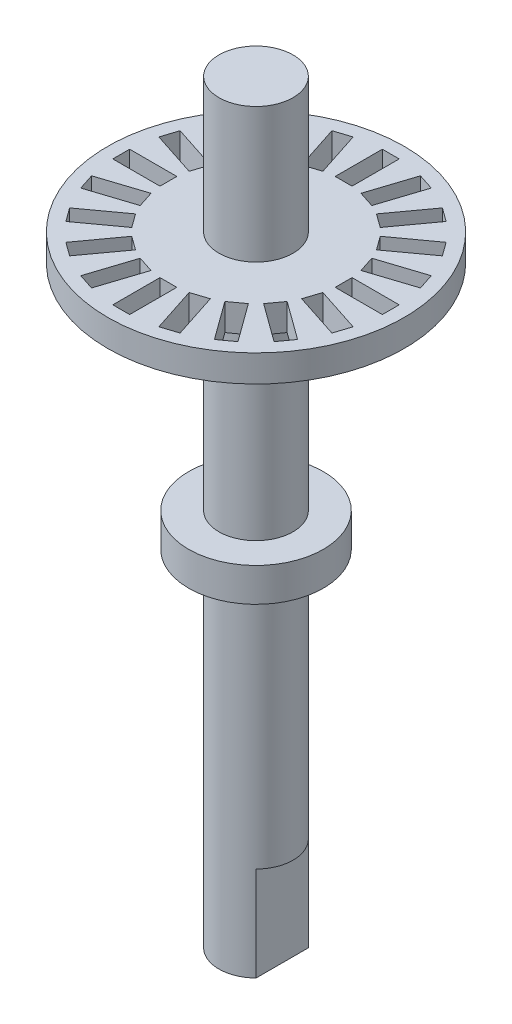
SolidWorks part; units mm, degrees
ref_plane "前视基准面" through (0, 0, 0) normal (0, 0, 1) x (1, 0, 0)
ref_plane "上视基准面" through (0, 0, 0) normal (0, 1, 0) x (1, 0, 0)
ref_plane "右视基准面" through (0, 0, 0) normal (1, 0, 0) x (0, 0, -1)
sketch "草图1" plane through (0, 0, 0) normal (0, 1, 0) x (1, 0, 0)
  circle A0 centre (0, 0) radius 2.75
  dimension "D1" = 5.5
extrude "凸台-拉伸1" add sketch "草图1" along normal blind 49
sketch "草图2" plane through (0, 0, 0) normal (0, -1, 0) x (1, 0, 0)
  line L0 (0, 0) -> (0, -4.8851) construction
  line L2 (-1.95, 1.9391) -> (-1.95, -1.9391)
  line L4 (1.95, 1.9391) -> (1.95, -1.9391)
  arc A0 (-1.95, -1.9391) -> (1.95, -1.9391) centre (0, 0) ccw
  arc A1 (1.95, 1.9391) -> (-1.95, 1.9391) centre (0, 0) ccw
  dimension "D1" = 5.5
  dimension "D2" = 3.9
extrude "凸台-拉伸2" add sketch "草图2" along normal blind 7
sketch "草图6" plane through (0, 49, 0) normal (0, 1, 0) x (1, 0, 0)
  line L2 (0, 11) -> (0, 0) construction
  line L3 (2.4958, 9.7037) -> (3.6846, 9.3174)
  line L42 (-0.625, 10) -> (0.625, 10)
  line L43 (-0.625, 10) -> (-0.625, 6.5)
  line L44 (-0.625, 6.5) -> (0.625, 6.5)
  line L45 (0.625, 10) -> (0.625, 6.5)
  line L46 (2.4958, 9.7037) -> (1.4142, 6.375)
  line L47 (1.4142, 6.375) -> (2.603, 5.9887)
  line L48 (3.6846, 9.3174) -> (2.603, 5.9887)
  line L49 (5.3722, 8.4575) -> (6.3835, 7.7228)
  line L50 (5.3722, 8.4575) -> (3.315, 5.626)
  line L51 (3.315, 5.626) -> (4.3262, 4.8912)
  line L52 (6.3835, 7.7228) -> (4.3262, 4.8912)
  line L53 (7.7228, 6.3835) -> (8.4575, 5.3722)
  line L54 (7.7228, 6.3835) -> (4.8912, 4.3262)
  line L55 (4.8912, 4.3262) -> (5.626, 3.315)
  line L56 (8.4575, 5.3722) -> (5.626, 3.315)
  line L57 (9.3174, 3.6846) -> (9.7037, 2.4958)
  line L58 (9.3174, 3.6846) -> (5.9887, 2.603)
  line L59 (5.9887, 2.603) -> (6.375, 1.4142)
  line L60 (9.7037, 2.4958) -> (6.375, 1.4142)
  line L61 (10, 0.625) -> (10, -0.625)
  line L62 (10, 0.625) -> (6.5, 0.625)
  line L63 (6.5, 0.625) -> (6.5, -0.625)
  line L64 (10, -0.625) -> (6.5, -0.625)
  line L65 (9.7037, -2.4958) -> (9.3174, -3.6846)
  line L66 (9.7037, -2.4958) -> (6.375, -1.4142)
  line L67 (6.375, -1.4142) -> (5.9887, -2.603)
  line L68 (9.3174, -3.6846) -> (5.9887, -2.603)
  line L69 (8.4575, -5.3722) -> (7.7228, -6.3835)
  line L70 (8.4575, -5.3722) -> (5.626, -3.315)
  line L71 (5.626, -3.315) -> (4.8912, -4.3262)
  line L72 (7.7228, -6.3835) -> (4.8912, -4.3262)
  line L73 (6.3835, -7.7228) -> (5.3722, -8.4575)
  line L74 (6.3835, -7.7228) -> (4.3262, -4.8912)
  line L75 (4.3262, -4.8912) -> (3.315, -5.626)
  line L76 (5.3722, -8.4575) -> (3.315, -5.626)
  line L77 (3.6846, -9.3174) -> (2.4958, -9.7037)
  line L78 (3.6846, -9.3174) -> (2.603, -5.9887)
  line L79 (2.603, -5.9887) -> (1.4142, -6.375)
  line L80 (2.4958, -9.7037) -> (1.4142, -6.375)
  line L81 (0.625, -10) -> (-0.625, -10)
  line L82 (0.625, -10) -> (0.625, -6.5)
  line L83 (0.625, -6.5) -> (-0.625, -6.5)
  line L84 (-0.625, -10) -> (-0.625, -6.5)
  line L85 (-2.4958, -9.7037) -> (-3.6846, -9.3174)
  line L86 (-2.4958, -9.7037) -> (-1.4142, -6.375)
  line L87 (-1.4142, -6.375) -> (-2.603, -5.9887)
  line L88 (-3.6846, -9.3174) -> (-2.603, -5.9887)
  line L89 (-5.3722, -8.4575) -> (-6.3835, -7.7228)
  line L90 (-5.3722, -8.4575) -> (-3.315, -5.626)
  line L91 (-3.315, -5.626) -> (-4.3262, -4.8912)
  line L92 (-6.3835, -7.7228) -> (-4.3262, -4.8912)
  line L93 (-7.7228, -6.3835) -> (-8.4575, -5.3722)
  line L94 (-7.7228, -6.3835) -> (-4.8912, -4.3262)
  line L95 (-4.8912, -4.3262) -> (-5.626, -3.315)
  line L96 (-8.4575, -5.3722) -> (-5.626, -3.315)
  line L97 (-9.3174, -3.6846) -> (-9.7037, -2.4958)
  line L98 (-9.3174, -3.6846) -> (-5.9887, -2.603)
  line L99 (-5.9887, -2.603) -> (-6.375, -1.4142)
  line L100 (-9.7037, -2.4958) -> (-6.375, -1.4142)
  line L101 (-10, -0.625) -> (-10, 0.625)
  line L102 (-10, -0.625) -> (-6.5, -0.625)
  line L103 (-6.5, -0.625) -> (-6.5, 0.625)
  line L104 (-10, 0.625) -> (-6.5, 0.625)
  line L105 (-9.7037, 2.4958) -> (-9.3174, 3.6846)
  line L106 (-9.7037, 2.4958) -> (-6.375, 1.4142)
  line L107 (-6.375, 1.4142) -> (-5.9887, 2.603)
  line L108 (-9.3174, 3.6846) -> (-5.9887, 2.603)
  line L109 (-8.4575, 5.3722) -> (-7.7228, 6.3835)
  line L110 (-8.4575, 5.3722) -> (-5.626, 3.315)
  line L111 (-5.626, 3.315) -> (-4.8912, 4.3262)
  line L112 (-7.7228, 6.3835) -> (-4.8912, 4.3262)
  line L113 (-6.3835, 7.7228) -> (-5.3722, 8.4575)
  line L114 (-6.3835, 7.7228) -> (-4.3262, 4.8912)
  line L115 (-4.3262, 4.8912) -> (-3.315, 5.626)
  line L116 (-5.3722, 8.4575) -> (-3.315, 5.626)
  line L117 (-3.6846, 9.3174) -> (-2.4958, 9.7037)
  line L118 (-3.6846, 9.3174) -> (-2.603, 5.9887)
  line L119 (-2.603, 5.9887) -> (-1.4142, 6.375)
  line L120 (-2.4958, 9.7037) -> (-1.4142, 6.375)
  circle A0 centre (0, 0) radius 11
  point P88 (0, 0)
  dimension "D1" = 22
  dimension "D3" = 10
  dimension "D4" = 6.5
  dimension "D2" = 1.25
extrude "凸台-拉伸4" add sketch "草图6" along normal blind 2 from offset 12 offset against normal yes
sketch "草图7" plane through (0, 49, 0) normal (0, 1, 0) x (1, 0, 0)
  circle A0 centre (0, 0) radius 5
  dimension "D1" = 10
extrude "凸台-拉伸5" add sketch "草图7" against normal blind 2.5 from offset 27.9 offset against normal yes
